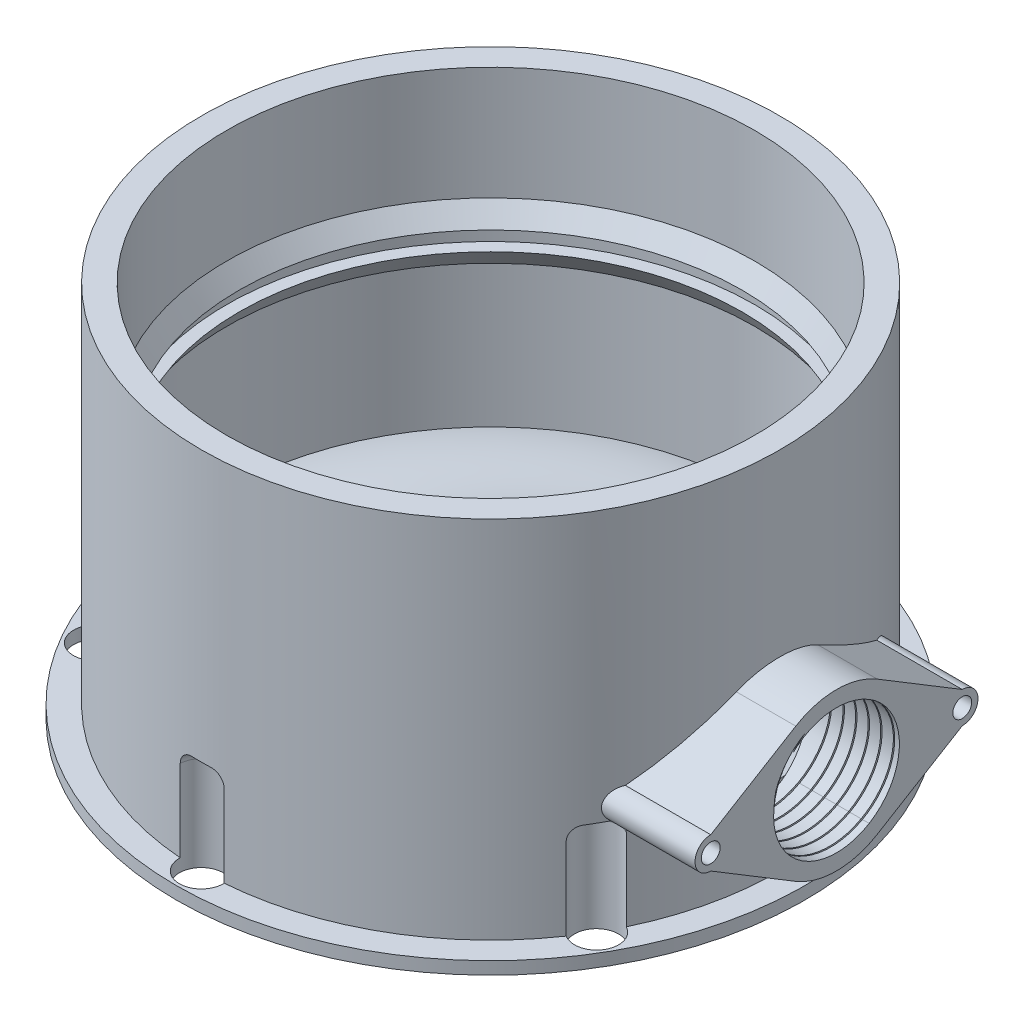
SolidWorks part; units mm, degrees
ref_plane "Front Plane" through (0, 0, 0) normal (0, 0, 1) x (1, 0, 0)
ref_plane "Top Plane" through (0, 0, 0) normal (0, 1, 0) x (1, 0, 0)
ref_plane "Right Plane" through (0, 0, 0) normal (1, 0, 0) x (0, 0, -1)
sketch "Sketch4" plane through (0, 0, 0) normal (0, 1, 0) x (1, 0, 0)
  circle A0 centre (0, 0) radius 53.34
  circle A1 centre (0, 0) radius 63.5
  dimension "D1" = 106.68
  dimension "D2" = 127
extrude "Boss-Extrude1" add sketch "Sketch4" along normal blind 2.54
sketch "Sketch6" plane through (0, 2.54, 0) normal (0, 1, 0) x (1, 0, 0)
  line L0 (0, -53.34) -> (0, -63.5) construction
  circle A0 centre (0, 0) radius 53.34 construction
  circle A1 centre (0, 0) radius 63.5 construction
  circle A2 centre (0, -58.42) radius 4.445
  dimension "D1" = 8.89
extrude "Cut-Extrude2" cut sketch "Sketch6" against normal blind 2.54
pattern_circular "CirPattern1" count 6 over 360 about axis through (0, 2.54, 0) along (0, 1, 0) of "Cut-Extrude2"
sketch "Sketch9" plane through (0, 2.54, 0) normal (0, 1, 0) x (1, 0, 0)
  circle A0 centre (0, 0) radius 58.42
  circle A1 centre (0, 0) radius 53.34
  dimension "D1" = 106.68
extrude "Boss-Extrude2" add sketch "Sketch9" along normal blind 73.66
extrude "Cut-Extrude3" cut sketch "Sketch6<2>" along normal blind 19.05
sketch "Sketch6<2>" plane through (0, 2.54, 0) normal (0, 1, 0) x (1, 0, 0) same geometry as "Sketch6"
fillet "Fillet1" radius 2.54 1 edges at (0, 21.59, 53.975)
pattern_circular "CirPattern3" count 6 over 360 about axis through (0, 76.2, 0) along (0, -1, 0) of "Fillet1", "Cut-Extrude3"
ref_plane "Plane7" through (69.85, 0, 0) normal (1, 0, 0) x (0, 0, -1)
sketch "Sketch10" plane through (69.85, 0, 0) normal (1, 0, 0) x (0, 0, -1)
  line L1 (-25.4, 27.305) -> (-8.2246, 37.7084)
  line L2 (-25.4, 20.955) -> (-8.2246, 10.5516)
  line L3 (0, 0) -> (0, 77.5888) construction
  line L4 (25.4, 27.305) -> (8.2246, 37.7084)
  line L5 (25.4, 20.955) -> (8.2246, 10.5516)
  line L8 (25.2788, 2.54) -> (-25.2788, 2.54) construction
  line L9 (63.5, 2.54) -> (-63.5, 2.54) construction
  arc A0 (-8.2246, 10.5516) -> (8.2246, 10.5516) centre (0, 24.13) ccw
  arc A1 (-25.4, 27.305) -> (-25.4, 20.955) centre (-25.4, 24.13) ccw
  arc A2 (25.4, 20.955) -> (25.4, 27.305) centre (25.4, 24.13) ccw
  circle A3 centre (0, 24.13) radius 12.7
  circle A4 centre (-25.4, 24.13) radius 1.905
  circle A5 centre (25.4, 24.13) radius 1.905
  arc A6 (8.2246, 37.7084) -> (-8.2246, 37.7084) centre (0, 24.13) ccw
  point P4 (0, 8.255)
  dimension "D1" = 31.75
  dimension "D2" = 6.35
  dimension "D3" = 6.35
  dimension "D4" = 25.4
  dimension "D6" = 25.4
  dimension "D7" = 3.81
  dimension "D8" = 3.81
  dimension "D9" = 21.59
  dimension "D5" = 25.4
  dimension "D10" = 5.715
extrude "Boss-Extrude3" add sketch "Sketch10" against normal up to surface (12.8271 mm away) up to face at (0, 76.2, 58.42)
sketch "Sketch11" plane through (69.85, 0, 0) normal (1, 0, 0) x (0, 0, -1)
  circle A0 centre (0, 24.13) radius 12.7
extrude "Cut-Extrude5" cut sketch "Sketch11" against normal up to surface (18.044 mm away) up to face at (0, 0, 53.34)
sketch "Sketch12" plane through (69.85, 0, 0) normal (1, 0, 0) x (0, 0, -1)
  circle A0 centre (0, 24.13) radius 12.7
curve "Helix/Spiral1" pitch 2.54 height 15.24 radius 12.7 centre (69.85, 24.13, 0) axis (-1, 0, 0) start towards (0, 0.7071, 0.7071)
ref_plane "Plane8" through (69.85, 33.1103, 8.9803) normal (-0.0318, 0.7067, -0.7067) x (0.9523, -0.1933, -0.2361)
sketch "Sketch13" plane through (69.85, 33.1103, 8.9803) normal (-0.0318, 0.7067, -0.7067) x (0.9523, -0.1933, -0.2361)
  line L1 (0, 0.381) -> (-0.254, 0.1905)
  line L2 (-0.254, 0.1905) -> (-0.254, -0.1905)
  line L3 (-0.254, -0.1905) -> (0, -0.381)
  line L4 (0, 0) -> (-0.254, 0) construction
  line L5 (0, 0.381) -> (0, -0.381)
  point P7 (0, 0)
  point P12 (-0.254, 0)
  dimension "D1" = 0.381
  dimension "D2" = 0.762
  dimension "D3" = 0.254
sweep "Cut-Sweep1" cut profiles "Sketch13" path "Helix/Spiral1" align with end faces yes
sketch "Sketch14" plane through (0, 0, 0) normal (0, 0, 1) x (1, 0, 0)
  line L0 (0, 0) -> (0, 31.75) construction
  line L1 (-53.34, 0) -> (53.34, 0) construction
  line L2 (0, 76.2) -> (0, 21.59) construction
  line L3 (6.35, 31.75) -> (6.35, 7.5944)
  line L4 (53.34, 13.2796) -> (53.34, 0) construction
  line L5 (6.35, 7.5944) -> (53.34, 7.5944)
  line L6 (53.34, 7.5944) -> (53.34, 13.2796)
  line L11 (50.8, 45.72) -> (53.34, 45.72)
  line L12 (53.34, 45.72) -> (53.34, 41.91)
  line L13 (53.34, 49.53) -> (50.8, 49.53)
  line L16 (53.34, 53.34) -> (53.34, 49.53)
  line L17 (50.8, 45.72) -> (53.34, 41.91)
  line L18 (53.34, 53.34) -> (50.8, 49.53)
  spline S1 degree 3 poles (6.35, 31.75) (9.8008, 26.6975) (17.151, 19.9797) (34.0829, 14.6451) (45.6422, 15.3114) (53.34, 13.2796) knots 0 0 0 0 0.349551 0.548128 1 1 1 1
  point P23 (52.07, 49.53)
  dimension "D2" = 6.35
  dimension "D4" = 3.81
  dimension "D3" = 53.34
  dimension "D1" = 31.75
  dimension "D5" = 53.34
  dimension "D6" = 3.81
  dimension "D7" = 2.54
revolve "Revolve1" add sketch "Sketch14" angle 360 about L0
